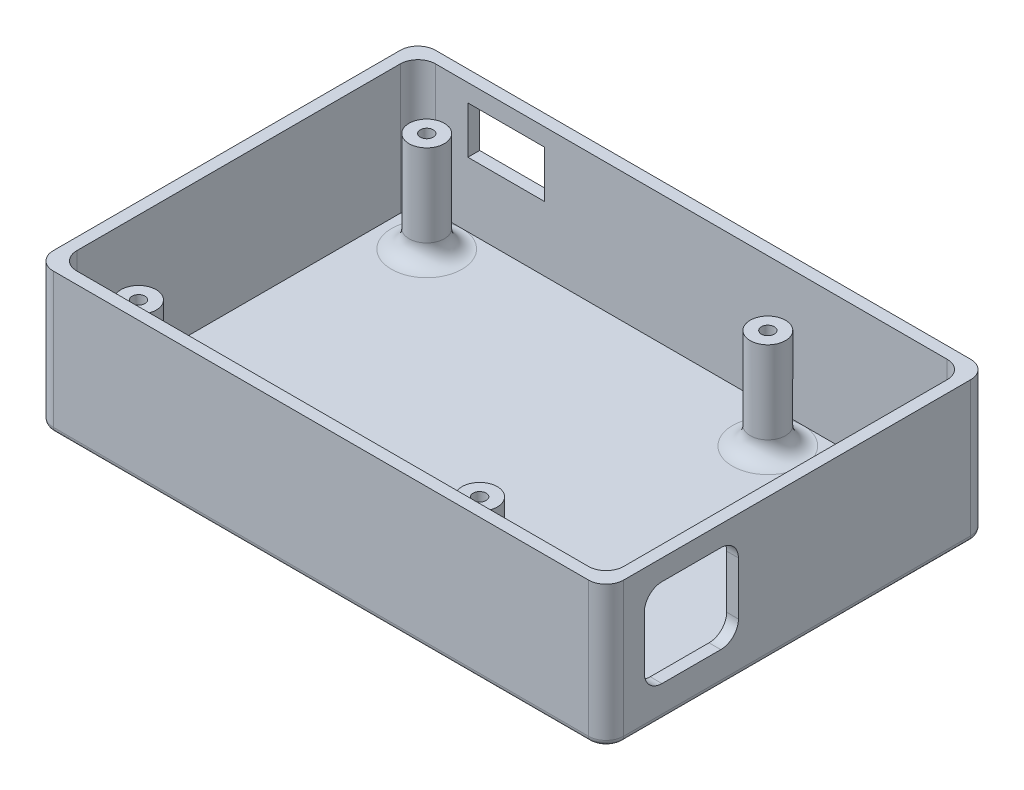
SolidWorks part; units mm, degrees
ref_plane "Front Plane" through (0, 0, 0) normal (0, 0, 1) x (1, 0, 0)
ref_plane "Top Plane" through (0, 0, 0) normal (0, 1, 0) x (1, 0, 0)
ref_plane "Right Plane" through (0, 0, 0) normal (1, 0, 0) x (0, 0, -1)
sketch "Sketch1" plane through (0, 0, 0) normal (0, 1, 0) x (1, 0, 0)
  line L1 (-48.5, 32.5) -> (48.5, 32.5)
  line L2 (-48.5, 32.5) -> (-48.5, -32.5)
  line L3 (-48.5, -32.5) -> (48.5, -32.5)
  line L4 (48.5, 32.5) -> (48.5, -32.5)
  line L5 (-48.5, 32.5) -> (48.5, -32.5) construction
  line L6 (-48.5, -32.5) -> (48.5, 32.5) construction
  point P0 (0, 0)
  dimension "D1" = 65
  dimension "D2" = 97
extrude "Boss-Extrude1" add sketch "Sketch1" along normal blind 2
sketch "Sketch3" plane through (0, 2, 0) normal (0, 1, 0) x (1, 0, 0)
  line L0 (46.5, 30.5) -> (-46.5, 30.5)
  line L1 (-46.5, 30.5) -> (-46.5, -30.5)
  line L2 (-46.5, -30.5) -> (46.5, -30.5)
  line L3 (46.5, -30.5) -> (46.5, 30.5)
  line L4 (48.5, -32.5) -> (48.5, 32.5)
  line L5 (48.5, 32.5) -> (-48.5, 32.5)
  line L6 (-48.5, 32.5) -> (-48.5, -32.5)
  line L7 (-48.5, -32.5) -> (48.5, -32.5)
  line L8 (48.5, -32.5) -> (48.5, 32.5)
  line L9 (48.5, 32.5) -> (-48.5, 32.5)
  line L10 (-48.5, 32.5) -> (-48.5, -32.5)
  line L11 (-48.5, -32.5) -> (48.5, -32.5)
  dimension "D1" = 0
  dimension "D2" = 2
extrude "Boss-Extrude2" add sketch "Sketch3" along normal blind 22
sketch "Sketch4" plane through (0, 2, 0) normal (0, 1, 0) x (1, 0, 0)
  line L0 (-46.5, 0) -> (46.5, 0) construction
  line L1 (-46.5, 30.5) -> (-46.5, -30.5) construction
  line L2 (46.5, -30.5) -> (46.5, 30.5) construction
  line L3 (-39, 27.7754) -> (-39, -22.5091) construction
  line L4 (-10, 25.9265) -> (-10, -25.8342) construction
  circle A0 centre (-39, 24.5) radius 3
  circle A1 centre (-39, -24.5) radius 3
  circle A2 centre (19, -24.5) radius 3
  circle A3 centre (19, 24.5) radius 3
  dimension "D1" = 6
  dimension "D2" = 49
  dimension "D3" = 58
  dimension "D4" = 27.5
extrude "Boss-Extrude3" add sketch "Sketch4" along normal blind 17
sketch "Sketch5" plane through (0, 19, 0) normal (0, 1, 0) x (1, 0, 0)
  circle A0 centre (-39, 24.5) radius 1.1
  circle A1 centre (19, 24.5) radius 1.1
  circle A2 centre (19, -24.5) radius 1.1
  circle A3 centre (-39, -24.5) radius 1.1
  dimension "D1" = 2.2
  dimension "D2" = 2.2
  dimension "D3" = 2.2
  dimension "D4" = 2.2
extrude "Cut-Extrude1" cut sketch "Sketch5" against normal blind 10
fillet "Fillet1" radius 3 4 edges at (-39, 2, 21.5) (19, 2, 27.5) (19, 2, -27.5) (-39, 2, -21.5)
fillet "Fillet2" radius 3 8 edges at (46.5, 13, -30.5) (48.5, 12, -32.5) (48.5, 12, 32.5) (46.5, 13, 30.5) (-46.5, 13, 30.5) (-48.5, 12, 32.5) (-48.5, 12, -32.5) (-46.5, 13, -30.5)
sketch "Sketch6" plane through (48.5, 0, 0) normal (1, 0, 0) x (0, 0, -1)
  line L0 (-18, 24) -> (-18, 0) construction
  line L1 (-29.5, 24) -> (29.5, 24) construction
  line L2 (-29.5, 0) -> (29.5, 0) construction
  line L3 (0, 0) -> (0, 24) construction
  line L4 (-26, 20.5) -> (-10, 20.5)
  line L5 (-26, 20.5) -> (-26, 5.5)
  line L6 (-26, 5.5) -> (-10, 5.5)
  line L7 (-10, 20.5) -> (-10, 5.5)
  line L8 (-26, 20.5) -> (-10, 5.5) construction
  line L9 (-26, 5.5) -> (-10, 20.5) construction
  point P6 (-18, 13)
  dimension "D1" = 16
  dimension "D2" = 15
  dimension "D3" = 18
  dimension "D4" = 13
extrude "Cut-Extrude2" cut sketch "Sketch6" against normal up to next
fillet "Fillet3" radius 3 4 edges at (47.5, 20.5, 26) (47.5, 20.5, 10) (47.5, 5.5, 10) (47.5, 5.5, 26)
sketch "Sketch7" plane through (0, 0, -32.5) normal (0, 0, -1) x (-1, 0, 0)
  line L0 (31.5, 24) -> (31.5, 0) construction
  line L1 (-45.5, 24) -> (45.5, 24) construction
  line L2 (-45.5, 0) -> (45.5, 0) construction
  line L3 (0, 0) -> (0, 24) construction
  line L4 (25, 21) -> (38, 21)
  line L5 (25, 21) -> (25, 13)
  line L6 (25, 13) -> (38, 13)
  line L7 (38, 21) -> (38, 13)
  line L8 (25, 21) -> (38, 13) construction
  line L9 (25, 13) -> (38, 21) construction
  point P6 (31.5, 17)
  dimension "D1" = 13
  dimension "D2" = 8
  dimension "D3" = 31.5
  dimension "D4" = 17
extrude "Cut-Extrude3" cut sketch "Sketch7" against normal up to next
fillet "Fillet4" radius 1 8 edges at (-47.6213, 0, -31.6213) (-48.5, 0, 0) (-47.6213, 0, 31.6213) (0, 0, 32.5) (47.6213, 0, 31.6213) (48.5, 0, 0) (47.6213, 0, -31.6213) (0, 0, -32.5)
